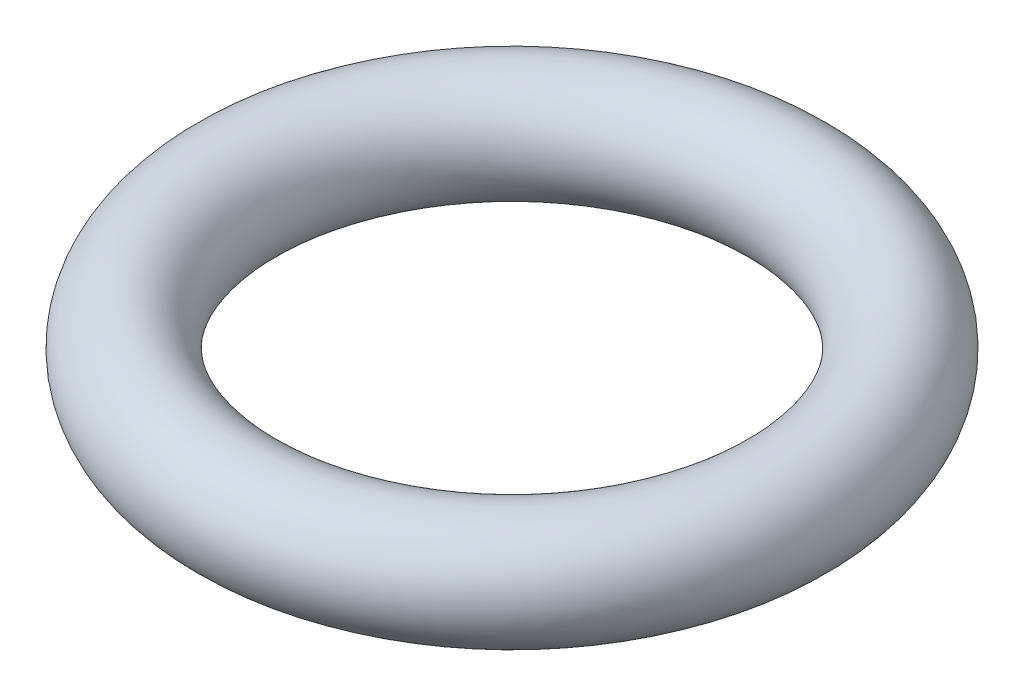
SolidWorks part; units mm, degrees
ref_plane "Front Plane" through (0, 0, 0) normal (0, 0, 1) x (1, 0, 0)
ref_plane "Top Plane" through (0, 0, 0) normal (0, 1, 0) x (1, 0, 0)
ref_plane "Right Plane" through (0, 0, 0) normal (1, 0, 0) x (0, 0, -1)
sketch "Sketch1" plane through (0, 0, 0) normal (0, 0, 1) x (1, 0, 0)
  line L0 (0, 0) -> (0, 24.0291) construction
  circle A0 centre (-50, 0) radius 10
  dimension "D2" = 20
  dimension "D3" = 50
revolve "Revolve1" add sketch "Sketch1" angle 360 about L0
equation "\"diameter\"=50"
equation "\"D3@Sketch1\"=\"diameter\""
equation "\"thickmess\"=20"
equation "\"D2@Sketch1\"=\"thickmess\""
